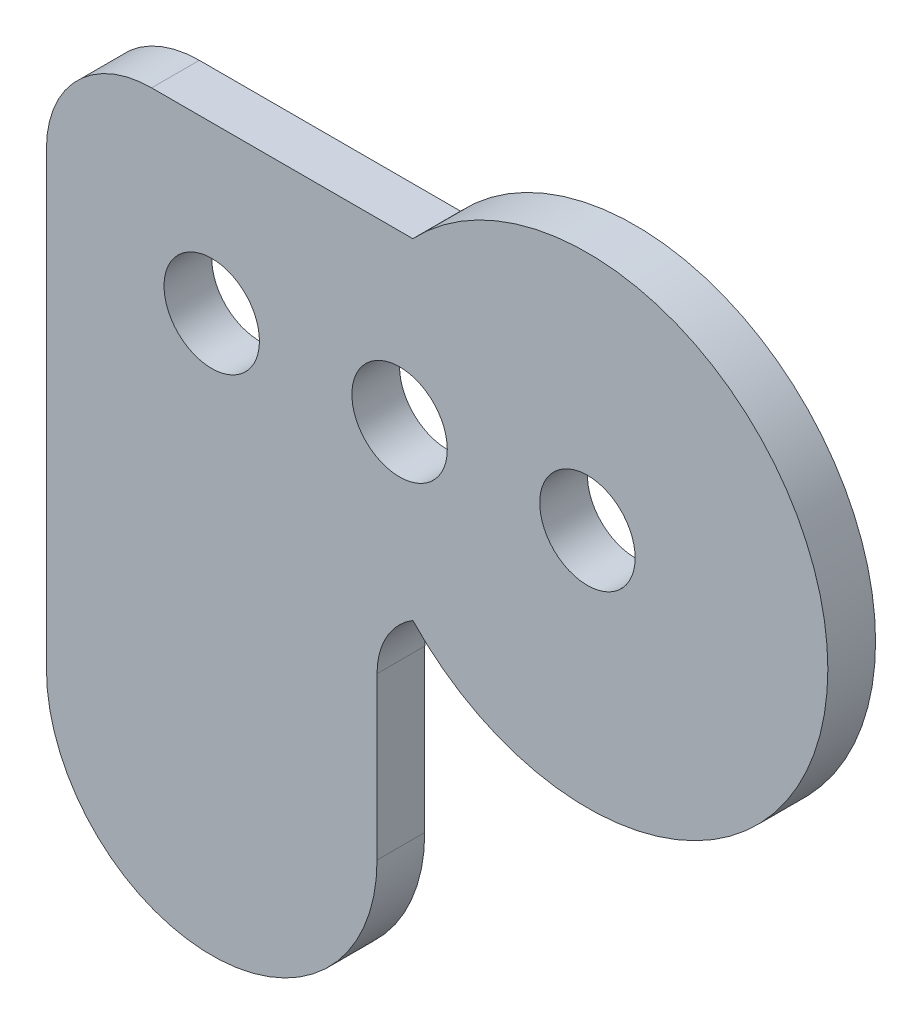
SolidWorks part; units mm, degrees
ref_plane "Front Plane" through (0, 0, 0) normal (0, 0, 1) x (1, 0, 0)
ref_plane "Top Plane" through (0, 0, 0) normal (0, 1, 0) x (1, 0, 0)
ref_plane "Right Plane" through (0, 0, 0) normal (1, 0, 0) x (0, 0, -1)
sketch "Sketch1" plane through (0, 0, 0) normal (0, 0, 1) x (1, 0, 0)
  line L0 (-11.619, 11) -> (-36, 11)
  line L1 (-36, 11) -> (-36, -26)
  line L2 (-14, -26) -> (-14, -11)
  line L3 (-14, -11) -> (-11.619, -11)
  arc A0 (-11.619, -11) -> (-11.619, 11) centre (0, 0) ccw
  arc A1 (-36, -26) -> (-14, -26) centre (-25, -26) ccw
  dimension "D1" = 32
  dimension "D7" = 25
  dimension "D2" = 11
  dimension "D3" = 11
  dimension "D4" = 26
  dimension "D6" = 22
extrude "Boss-Extrude1" add sketch "Sketch1" along normal blind 3.175
fillet "Fillet1" radius 7 1 edges at (-36, 11, 1.5875)
fillet "Fillet2" radius 5 1 edges at (-14, -11, 1.5875)
sketch "Sketch2" plane through (0, 0, 3.175) normal (0, 0, 1) x (1, 0, 0)
  circle A0 centre (0, 0) radius 3.175
  dimension "D1" = 6.35
extrude "Cut-Extrude1" cut sketch "Sketch2" against normal through all
pattern_linear "LPattern1" count 3 spacing 12.5 along (-1, 0, 0) of "Cut-Extrude1"
